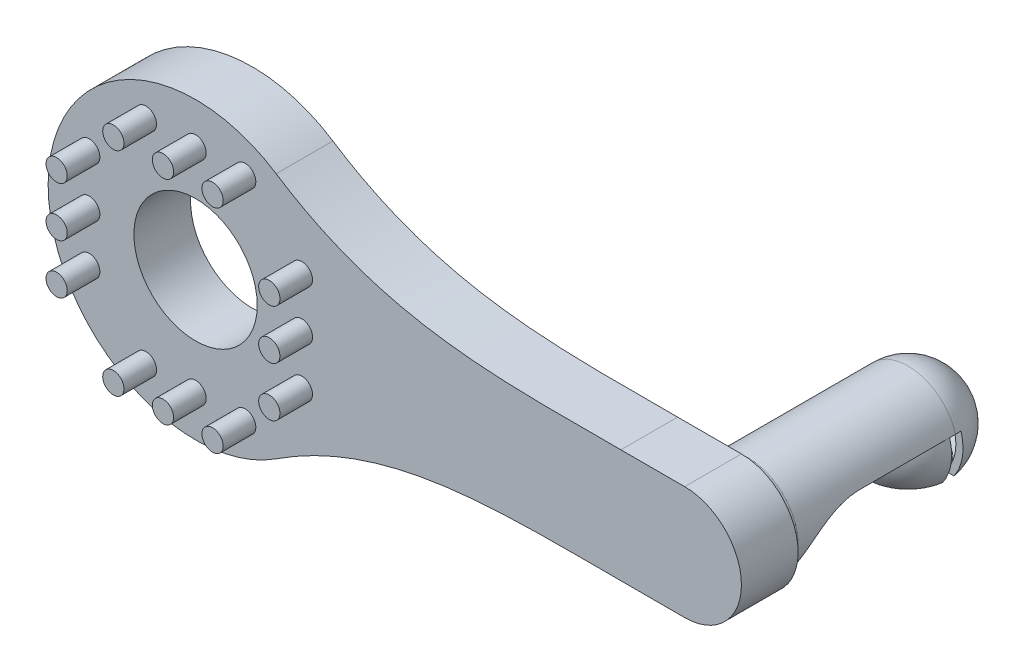
SolidWorks part; units mm, degrees
ref_plane "Front Plane" through (0, 0, 0) normal (0, 0, 1) x (1, 0, 0)
ref_plane "Top Plane" through (0, 0, 0) normal (0, 1, 0) x (1, 0, 0)
ref_plane "Right Plane" through (0, 0, 0) normal (1, 0, 0) x (0, 0, -1)
sketch "Sketch1" plane through (0, 0, 0) normal (0, 0, 1) x (1, 0, 0)
  line L0 (0, 0) -> (52.669, 0) construction
  line L1 (30, 4) -> (34.5, 4)
  line L2 (30, -4) -> (34.5, -4)
  arc A0 (5.6862, 8.7079) -> (5.6862, -8.7079) centre (0, 0) ccw
  circle A1 centre (0, 0) radius 4.35
  arc A2 (34.5, 4) -> (34.5, -4) centre (34.5, 0) cw
  circle A3 centre (34.5, 0) radius 1
  spline S0 degree 3 poles (5.6862, 8.7079) (13.4104, 3.664) (21.2669, 4) (30, 4) knots 0 0 0 0 1 1 1 1
  spline S1 degree 3 poles (5.6862, -8.7079) (13.4104, -3.664) (21.2669, -4) (30, -4) knots 0 0 0 0 1 1 1 1
  dimension "D1" = 20.8
  dimension "D2" = 8.7
  dimension "D8" = 34.5
  dimension "D7" = 2
  dimension "D3" = 4
  dimension "D4" = 4.5
  dimension "D5" = 17.1959
  dimension "D6" = 30
extrude "Boss-Extrude1" add sketch "Sketch1" along normal blind 4
sketch "Sketch2" plane through (0, 0, 4) normal (0, 0, 1) x (1, 0, 0)
  line L0 (0, -55) -> (0, 55) construction
  line L1 (55, 0) -> (-55, 0) construction
  circle A0 centre (0, 0) radius 10.4 construction
  circle A1 centre (0, 0) radius 4.35 construction
  circle A2 centre (0, 7.5) radius 0.75
  circle A3 centre (3.5, 7.5) radius 0.75
  circle A4 centre (-3.5, 7.5) radius 0.75
  circle A5 centre (3.5, -7.5) radius 0.75
  circle A6 centre (0, -7.5) radius 0.75
  circle A7 centre (-3.5, -7.5) radius 0.75
  circle A8 centre (7.5, 0) radius 0.75
  circle A9 centre (7.5, 3.5) radius 0.75
  circle A10 centre (7.5, -3.5) radius 0.75
  circle A11 centre (-7.5, -3.5) radius 0.75
  circle A12 centre (-7.5, 0) radius 0.75
  circle A13 centre (-7.5, 3.5) radius 0.75
  dimension "D1" = 20.8
  dimension "D2" = 8.7
  dimension "D3" = 1.5
  dimension "D5" = 1.5
  dimension "D9" = 1.5
  dimension "D12" = 1.5
  dimension "D4" = 7.5
  dimension "D6" = 3.5
  dimension "D7" = 0
  dimension "D8" = 0
  dimension "D10" = 7.5
  dimension "D11" = 0
  dimension "D13" = 3.5
  dimension "D14" = 0
extrude "Boss-Extrude2" add sketch "Sketch2" along normal blind 2.3
ref_plane "Plane1" through (0, 0, -11.75) normal (0, 0, -1) x (-1, 0, 0)
sketch "Sketch5" plane through (0, 0, 0) normal (0, 1, 0) x (1, 0, 0)
  line L0 (11.44, 11.75) -> (-11.44, 11.75) construction
  line L2 (38, 11.75) -> (37.5, 11.75)
  line L3 (31.5, 11.75) -> (31, 11.75)
  arc A0 (38, 11.75) -> (31, 11.75) centre (34.5, 11.75) ccw
  arc A1 (37.5, 11.75) -> (31.5, 11.75) centre (34.5, 11.75) ccw
  point P0 (34.5, 11.75)
  dimension "D3" = 3.5
  dimension "D4" = 3
  dimension "D1" = 0
  dimension "D2" = 34.5
revolve "Revolve1" add sketch "Sketch5" angle 360 about L2
ref_plane "Plane2" through (0, -2, 0) normal (0, 1, 0) x (1, 0, 0)
sketch "Sketch7" plane through (0, -2, 0) normal (0, 1, 0) x (1, 0, 0)
  circle A0 centre (34.5, 11.75) radius 2.8723
  circle A1 centre (34.5, 11.75) radius 2.8723
  circle A2 centre (34.5, 11.75) radius 3.5
  dimension "D1" = 7
  dimension "D2" = 0
extrude "Cut-Extrude2" cut sketch "Sketch7" against normal through all contours A1
sketch "Sketch9" plane through (0, -2, 0) normal (0, 1, 0) x (1, 0, 0)
  line L0 (34.9, 11.35) -> (37.9771, 11.35)
  line L2 (34.1, 8.2729) -> (34.1, 11.35)
  line L4 (34.9, 8.2729) -> (34.9, 11.35)
  line L5 (31.0229, 11.35) -> (34.1, 11.35)
  line L7 (31.0229, 12.15) -> (34.1, 12.15)
  line L9 (34.9, 12.15) -> (34.9, 15.2271)
  line L10 (34.9, 12.15) -> (37.9771, 12.15)
  line L11 (34.1, 12.15) -> (34.1, 15.2271)
  circle A1 centre (34.5, 11.75) radius 2.2361 construction
  arc A2 (34.1, 8.2729) -> (34.9, 8.2729) centre (34.5, 11.75) ccw
  arc A3 (37.9771, 11.35) -> (37.9771, 12.15) centre (34.5, 11.75) ccw
  arc A4 (34.9, 15.2271) -> (34.1, 15.2271) centre (34.5, 11.75) ccw
  arc A5 (31.0229, 12.15) -> (31.0229, 11.35) centre (34.5, 11.75) ccw
  point P1 (38, 11.75)
  point P2 (34.5, 8.25)
  point P3 (34.5, 15.25)
  point P12 (31, 11.75)
  dimension "D2" = 0.8
  dimension "D3" = 0.4
  dimension "D4" = 0.8
  dimension "D5" = 0.4
  dimension "D1" = 7
extrude "Cut-Extrude3" cut sketch "Sketch9" along normal blind 3 contours L9 A4 L11 L7 A5 L5 L2 A2 L4 L0 A3 L10
sketch "Sketch10" plane through (0, 0, -11.75) normal (0, 0, -1) x (-1, 0, 0)
  line L0 (-37.8541, 1) -> (-31.1459, 1)
  arc A0 (-31.1459, 1) -> (-37.8541, 1) centre (-34.5, 0) ccw
  arc A1 (-31.1459, 1) -> (-37.8541, 1) centre (-34.5, 0) ccw
sketch "Sketch13" plane through (0, 0, 0) normal (0, 0, -1) x (-1, 0, 0)
  circle A0 centre (-34.5, 0) radius 1
extrude "Boss-Extrude3" add sketch "Sketch13" against normal up to surface (4 mm away) up to face at (-8.25, 3.5, 4)
sketch "Sketch17" plane through (0, 0, 0) normal (0, 0, -1) x (-1, 0, 0)
  line L0 (-37.8541, 1) -> (-31.1459, 1)
  line L1 (-37.8541, 1) -> (-31.1459, 1) construction
  arc A0 (-31.1459, 1) -> (-37.8541, 1) centre (-34.5, 0) ccw
  dimension "D1" = 7
extrude "Boss-Extrude4" add sketch "Sketch17" along normal up to surface (11.75 mm away) contours L0 A0 up to face at (34.5, -0.5279, -11.75)
fillet "Fillet3" radius 0.5 1 edges at (34.5, 3.5, 0)
fillet "Fillet5" radius 5 1 edges at (34.5, 1, 0)
equation "\"D3@Sketch9\"=\"D2@Sketch9\"/2"
equation "\"D4@Sketch9\"=\"D2@Sketch9\""
equation "\"D5@Sketch9\"=\"D3@Sketch9\""
